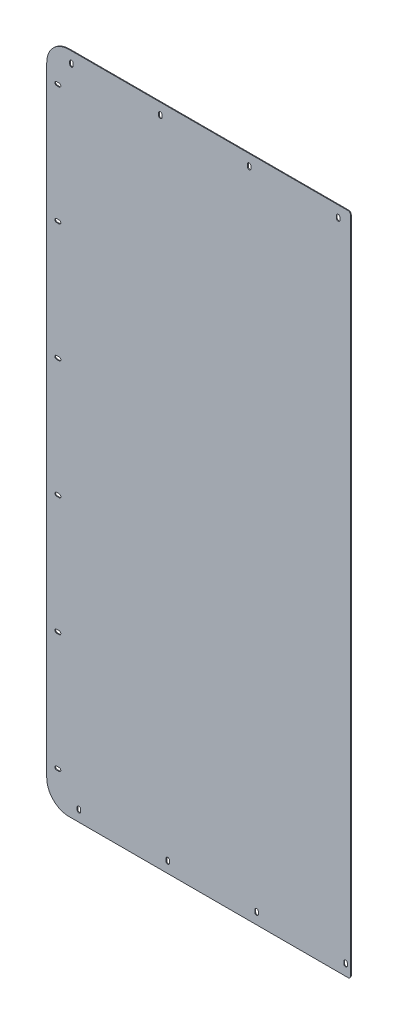
SolidWorks part; units mm, degrees
material "Q235-A"
ref_plane "前视基准面" through (0, 0, 0) normal (0, 0, 1) x (1, 0, 0)
ref_plane "上视基准面" through (0, 0, 0) normal (0, 1, 0) x (1, 0, 0)
ref_plane "右视基准面" through (0, 0, 0) normal (1, 0, 0) x (0, 0, -1)
sketch "草图1" plane through (0, 0, 0) normal (0, 0, 1) x (1, 0, 0)
  line L1 (307.5, -672.5) -> (-307.5, -672.5)
  line L2 (307.5, -672.5) -> (307.5, 672.5)
  line L3 (307.5, 672.5) -> (-307.5, 672.5)
  line L4 (-307.5, -672.5) -> (-307.5, 672.5)
  line L5 (307.5, -672.5) -> (-307.5, 672.5) construction
  line L6 (307.5, 672.5) -> (-307.5, -672.5) construction
  point P0 (0, 0)
  dimension "D1" = 1345
  dimension "D2" = 615
base flange "基体-法兰1" sketch "草图1" thickness 1.5 reverse thickness direction no parameters "D1"=0.7366
fillet "圆角1" radius 45 2 edges at (-307.5, 672.5, -0.75) (-307.5, -672.5, -0.75)
fillet "圆角2" radius 5 2 edges at (307.5, -672.5, -0.75) (307.5, 672.5, -0.75)
sketch "草图3" plane through (0, 0, 0) normal (0, 0, 1) x (1, 0, 0)
  line L0 (-287.5, -600) -> (-282.5, -600) construction
  line L1 (-287.5, -596.5) -> (-282.5, -596.5)
  line L2 (-287.5, -603.5) -> (-282.5, -603.5)
  line L3 (-307.5, 627.5) -> (-307.5, -627.5) construction
  line L4 (-262.5, -672.5) -> (302.5, -672.5) construction
  arc A0 (-287.5, -596.5) -> (-287.5, -603.5) centre (-287.5, -600) ccw
  arc A1 (-282.5, -603.5) -> (-282.5, -596.5) centre (-282.5, -600) ccw
  point P2 (-285, -600)
  dimension "D1" = 7
  dimension "D2" = 5
  dimension "D3" = 22.5
  dimension "D4" = 72.5
extrude "切除-拉伸2" cut sketch "草图3" against normal blind 10 normal cut yes
pattern_linear "阵列(线性)1" count 6 spacing 240 along (0, 1, 0) of "切除-拉伸2"
sketch "草图4" plane through (0, 0, 0) normal (0, 0, 1) x (1, 0, 0)
  line L0 (-257.5, 647.5) -> (-257.5, 652.5) construction
  line L1 (-261, 647.5) -> (-261, 652.5)
  line L2 (-254, 647.5) -> (-254, 652.5)
  line L3 (-242.5, -652.5) -> (-242.5, -647.5) construction
  line L4 (-246, -652.5) -> (-246, -647.5)
  line L5 (-239, -652.5) -> (-239, -647.5)
  line L6 (-262.5, -672.5) -> (302.5, -672.5) construction
  line L7 (302.5, 672.5) -> (-262.5, 672.5) construction
  line L8 (-307.5, 627.5) -> (-307.5, -627.5) construction
  arc A0 (-261, 647.5) -> (-254, 647.5) centre (-257.5, 647.5) ccw
  arc A1 (-254, 652.5) -> (-261, 652.5) centre (-257.5, 652.5) ccw
  arc A2 (-246, -652.5) -> (-239, -652.5) centre (-242.5, -652.5) ccw
  arc A3 (-239, -647.5) -> (-246, -647.5) centre (-242.5, -647.5) ccw
  point P2 (-257.5, 650)
  point P9 (-242.5, -650)
  dimension "D8" = 65
  dimension "D1" = 7
  dimension "D2" = 5
  dimension "D3" = 7
  dimension "D4" = 5
  dimension "D5" = 22.5
  dimension "D6" = 22.5
  dimension "D7" = 50
extrude "切除-拉伸3" cut sketch "草图4" against normal blind 10 normal cut yes
pattern_linear "阵列(线性)2" count 4 spacing 180 along (1, 0, 0) of "切除-拉伸3"
sketch "折弯-线1" [suppressed] plane through (0, 0, 0) normal (0, 1, 0) x (1, 0, 0)
sketch "边界框1" [suppressed] plane through (0, 0, 0) normal (0, 1, 0) x (1, 0, 0)
sheet metal parameters "钣金1" thickness 1.5 parameters "D1"=0.7366
flat pattern "平板型式1" [suppressed]
sketch "折弯-线2" plane through (0, 0, 0) normal (0, 1, 0) x (1, 0, 0)
sketch3d "边界框2" [suppressed]
  line L0 (307.5, -672.5, 0) -> (307.5, 672.5, 0) construction
  line L1 (-307.5, -672.5, 0) -> (-307.5, 672.5, 0) construction
  line L2 (307.5, -672.5, 0) -> (-307.5, -672.5, 0) construction
  line L3 (307.5, 672.5, 0) -> (-307.5, 672.5, 0) construction
sheet metal parameters "钣金3" thickness 1.5 parameters "D1"=0.7366
flat pattern "平板型式1"
sketch "折弯-线2" plane through (0, 0, 0) normal (0, 1, 0) x (1, 0, 0)
sketch3d "边界框2" [suppressed]
  line L0 (307.5, -672.5, 0) -> (307.5, 672.5, 0) construction
  line L1 (-307.5, -672.5, 0) -> (-307.5, 672.5, 0) construction
  line L2 (307.5, -672.5, 0) -> (-307.5, -672.5, 0) construction
  line L3 (307.5, 672.5, 0) -> (-307.5, 672.5, 0) construction
sheet metal parameters "钣金4" thickness 1.5 parameters "D1"=0.7366
flat pattern "平板型式1"
sketch "折弯-线2" plane through (0, 0, 0) normal (0, 1, 0) x (1, 0, 0)
sketch3d "边界框2" [suppressed]
  line L0 (307.5, -672.5, 0) -> (307.5, 672.5, 0) construction
  line L1 (-307.5, -672.5, 0) -> (-307.5, 672.5, 0) construction
  line L2 (307.5, -672.5, 0) -> (-307.5, -672.5, 0) construction
  line L3 (307.5, 672.5, 0) -> (-307.5, 672.5, 0) construction
sheet metal parameters "钣金5" thickness 1.5 parameters "D1"=0.7366
flat pattern "平板型式1"
sketch "折弯-线2" plane through (0, 0, 0) normal (0, 1, 0) x (1, 0, 0)
sketch3d "边界框2" [suppressed]
  line L0 (307.5, -672.5, 0) -> (307.5, 672.5, 0) construction
  line L1 (-307.5, -672.5, 0) -> (-307.5, 672.5, 0) construction
  line L2 (307.5, -672.5, 0) -> (-307.5, -672.5, 0) construction
  line L3 (307.5, 672.5, 0) -> (-307.5, 672.5, 0) construction
sheet metal parameters "钣金6" thickness 1.5 parameters "D1"=0.7366
flat pattern "平板型式1" [suppressed]
sketch "折弯-线2" plane through (0, 0, 0) normal (0, 1, 0) x (1, 0, 0)
sketch3d "边界框2" [suppressed]
  line L0 (307.5, -672.5, 0) -> (307.5, 672.5, 0) construction
  line L1 (-307.5, -672.5, 0) -> (-307.5, 672.5, 0) construction
  line L2 (307.5, -672.5, 0) -> (-307.5, -672.5, 0) construction
  line L3 (307.5, 672.5, 0) -> (-307.5, 672.5, 0) construction
sketch "草图2-1" [suppressed] plane through (0, 0, -1.5) normal (0, 0, -1) x (-1, 0, 0)
  line L1 (-307.5, -667.5) -> (-307.5, 667.5) construction
  line L2 (-302.5, 672.5) -> (262.5, 672.5) construction
  circle A0 centre (-207.5, 572.5) radius 15
  dimension "D1" = 30
  dimension "D2" = 100
  dimension "D3" = 100
